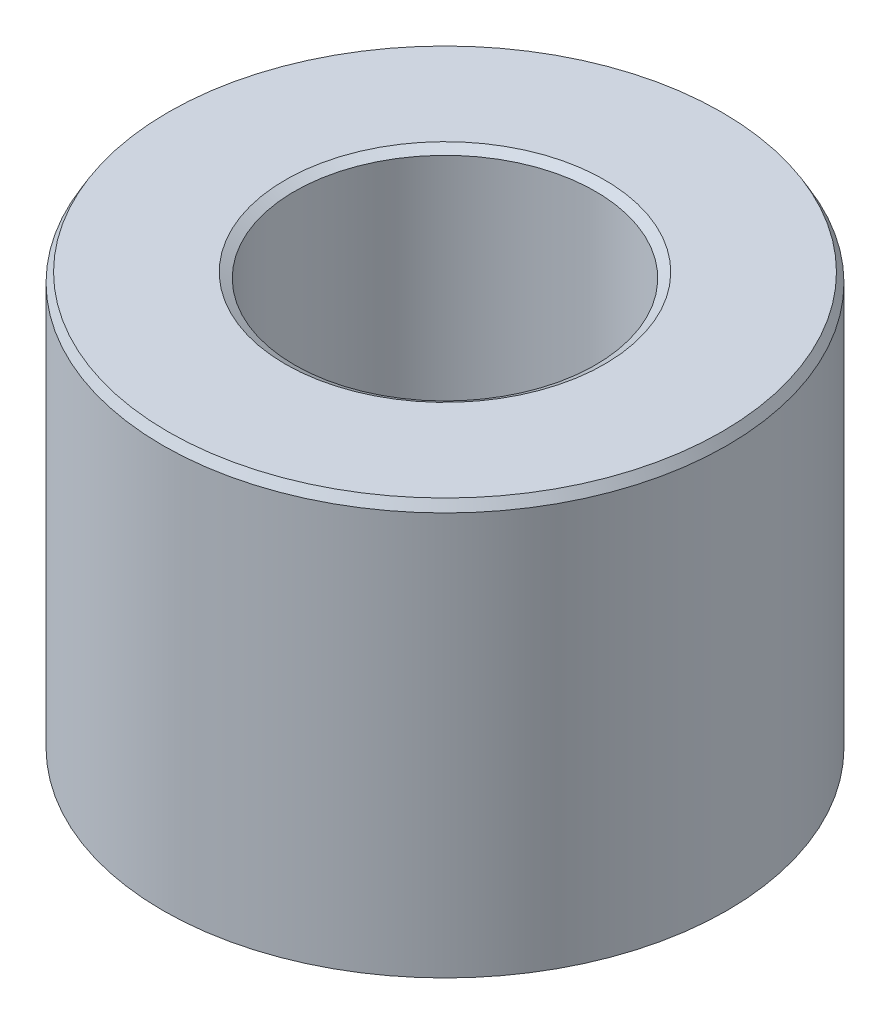
SolidWorks part; units mm, degrees
ref_plane "Front Plane" through (0, 0, 0) normal (0, 0, 1) x (1, 0, 0)
ref_plane "Top Plane" through (0, 0, 0) normal (0, 1, 0) x (1, 0, 0)
ref_plane "Right Plane" through (0, 0, 0) normal (1, 0, 0) x (0, 0, -1)
sketch "Sketch1" plane through (0, 0, 0) normal (0, 1, 0) x (1, 0, 0)
  circle A0 centre (0, 0) radius 40
  dimension "SLEEVE_OD" = 80
extrude "Boss-Extrude1" add sketch "Sketch1" along normal blind 59.1532
sketch "Sketch2" plane through (0, 0, 0) normal (0, 1, 0) x (1, 0, 0)
  circle A0 centre (0, 0) radius 21.3318
  dimension "BORE_D" = 42.6637
extrude "Cut-Extrude1" cut sketch "Sketch2" along normal through all
chamfer "Chamfer1" distance 1.3031 angle 30 4 edges at (0, 59.1532, 21.3318) (0, 0, 21.3318) (0, 0, 40) (0, 59.1532, 40) first distance on face at (0, 59.1532, 21.3318) first distance on face at (0, 0, 21.3318) first distance on face at (0, 59.1532, 40)
